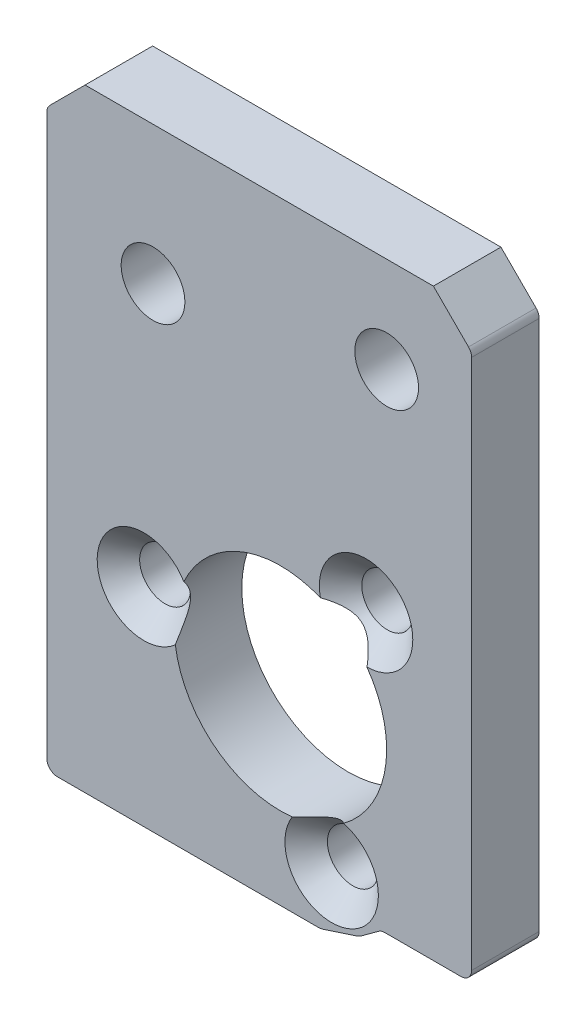
SolidWorks part; units mm, degrees
ref_plane "Front Plane" through (0, 0, 0) normal (0, 0, 1) x (1, 0, 0)
ref_plane "Top Plane" through (0, 0, 0) normal (0, 1, 0) x (1, 0, 0)
ref_plane "Right Plane" through (0, 0, 0) normal (1, 0, 0) x (0, 0, -1)
sketch "Sketch1" plane through (0, 0, 0) normal (0, 0, 1) x (1, 0, 0)
  line L1 (0, 0) -> (20, 0)
  line L2 (0, 0) -> (0, 29.11)
  line L3 (0, 29.11) -> (20, 29.11)
  line L4 (20, 0) -> (20, 29.11)
  circle A0 centre (5, 22.61) radius 1.5
  circle A1 centre (16, 24.61) radius 1.5
  arc A2 (15.0728, 12.0104) -> (12.8801, 13.743) centre (15.03, 14.21) ccw
  arc A3 (6.4499, 11.1828) -> (6.049, 8.4114) centre (4.57, 10.04) ccw
  arc A4 (11.5537, 4.1408) -> (13.9699, 5.0876) centre (13.41, 2.96) ccw
  circle A7 centre (15.03, 14.21) radius 1.2
  circle A8 centre (4.57, 10.04) radius 1.2
  circle A9 centre (13.41, 2.96) radius 1.2
  circle A10 centre (11, 9.11) radius 5
  point P14 (0, 0)
  point P24 (0, 0)
  point P25 (16, 24.61)
  point P27 (0, 0)
  point P28 (15, 24.61)
  point P30 (0, 0)
  point P31 (16, 24.61)
extrude "Boss-Extrude2" add sketch "Sketch1" against normal blind 3.18 contours A0 | A1 | L2 L1 L4 L3 | A7 | A10 | A8 | A9 region at (5, 22.61, 0) region at (16, 24.61, 0)
hole_wizard "CSK for M2 Flat Head Machine Screw1" positions "Sketch10" profile "Sketch11" countersink size "M2" standard "ANSI Metric"
sketch "Sketch10" plane through (0, 0, 0) normal (0, 0, 1) x (1, 0, 0)
  point P0 (4.57, 10.04)
  point P3 (15.03, 14.21)
  point P6 (13.41, 2.96)
sketch "Sketch11" plane through (4.57, 10.04, 0) normal (1, 0, 0) x (0, -1, 0)
  line L0 (0, 0) -> (0, 4.23)
  line L1 (0, 4.23) -> (1.2, 3.509)
  line L2 (1.2, 3.509) -> (1.2, 1)
  line L3 (1.2, 1) -> (2.2, 0)
  line L5 (2.2, 0) -> (0, 0)
  line L6 (-1.2, 1) -> (-2.2, 0) construction
  line L10 (0, 4.23) -> (-1.2, 3.509) construction
  line L11 (0, -6.35) -> (0, 107.95) construction
  dimension "Hole Dia." = 2.4
  dimension "Hole Depth" = 4.23
  dimension "Near C'Sink Dia." = 4.4
  dimension "Near C'Sink Angle" = 90
  dimension "Drill Angle" = 118
chamfer "Chamfer1" distance 1.8 angle 45 2 edges at (0, 29.11, -1.59) (20, 29.11, -1.59)
fillet "Fillet1" radius 0.5 2 edges at (20, 27.31, -1.59) (0, 27.31, -1.59)
sketch "Sketch12" plane through (0, 0, -3.18) normal (0, 0, -1) x (-1, 0, 0)
  line L0 (0, 0) -> (-20, 0)
  line L1 (0, 0) -> (-20, 0) construction
  line L2 (-20, 0) -> (-20, 1.6068)
  line L3 (-20, 0) -> (-20, 27.1029) construction
  line L4 (-20, 1.6068) -> (-15.7486, 1.6068)
  line L6 (0, 0) -> (-20, 0) construction
  line L8 (0, 0.2514) -> (-13.8989, 0.2514)
  line L9 (-13.8989, 0.2514) -> (-15.7486, 1.6068)
  line L10 (0, 0) -> (0, 27.1029) construction
  line L11 (0, 0.2514) -> (0, 0)
extrude "Cut-Extrude1" cut sketch "Sketch12" against normal blind 4
fillet "Fillet6" radius 0.5 3 edges at (0, 0.2514, -1.59) (15.7486, 1.6068, -1.59) (20, 1.6068, -1.59)
sketch "Sketch14" plane through (0, 0, 0) normal (0, 0, 1) x (1, 0, 0)
  line L0 (12.8989, 0.2514) -> (13.8989, 0.2514)
  line L1 (13.8989, 0.2514) -> (0.5, 0.2514) construction
  line L2 (13.8989, 0.2514) -> (14.7055, 0.8424)
  line L3 (15.6166, 1.5101) -> (13.8989, 0.2514) construction
  line L4 (14.7055, 0.8424) -> (12.8989, 0.2514)
extrude "Cut-Extrude2" cut sketch "Sketch14" against normal blind 4
fillet "Fillet8" radius 1 2 edges at (12.8989, 0.2514, -1.59) (14.7055, 0.8424, -1.59)
